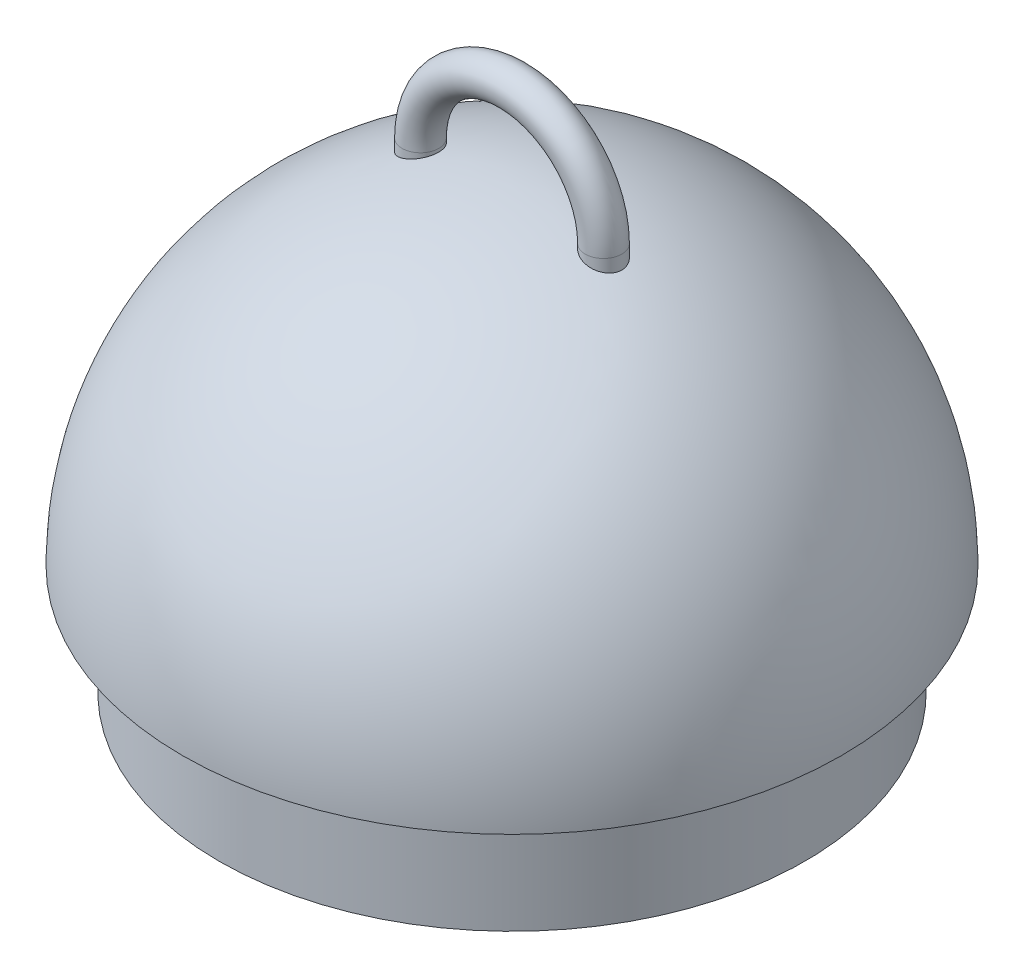
SolidWorks part; units mm, degrees
ref_plane "Front Plane" through (0, 0, 0) normal (0, 0, 1) x (1, 0, 0)
ref_plane "Top Plane" through (0, 0, 0) normal (0, 1, 0) x (1, 0, 0)
ref_plane "Right Plane" through (0, 0, 0) normal (1, 0, 0) x (0, 0, -1)
sketch "Sketch1" plane through (0, 0, 0) normal (0, 1, 0) x (1, 0, 0)
  circle A0 centre (0, 0) radius 80
  dimension "D1" = 160
extrude "Case Mate" add sketch "Sketch1" along normal blind 30
sketch "Sketch2" plane through (0, 30, 0) normal (0, 1, 0) x (1, 0, 0)
  line L0 (90, 0) -> (-90, 0)
  arc A1 (90, 0) -> (-90, 0) centre (0, 0) ccw
  dimension "D1" = 180
revolve "Circular Cap" add sketch "Sketch2" angle 180 about L0 reverse direction yes
sketch "Sketch3" plane through (0, 0, 0) normal (0, -1, 0) x (-1, 0, 0)
  line L0 (-25, 0) -> (25, 0) construction
  circle A0 centre (25, 0) radius 5
  circle A1 centre (-25, 0) radius 5
  circle A3 centre (0, 0) radius 80 construction
  dimension "D1" = 10
  dimension "D2" = 10
  dimension "D4" = 25
  dimension "D5" = 25
  dimension "D6" = 0
  dimension "D3" = 50
extrude "Ring Base" add sketch "Sketch3" against normal blind 118.618
sketch "Sketch4" plane through (0, 118.618, 0) normal (0, 1, 0) x (1, 0, 0)
  line L0 (0, 0) -> (0, 21.9664) construction
  circle A0 centre (-25, 0) radius 5
  dimension "D1" = 10
revolve "Ring Revolve" add sketch "Sketch4" angle 180 about L0
